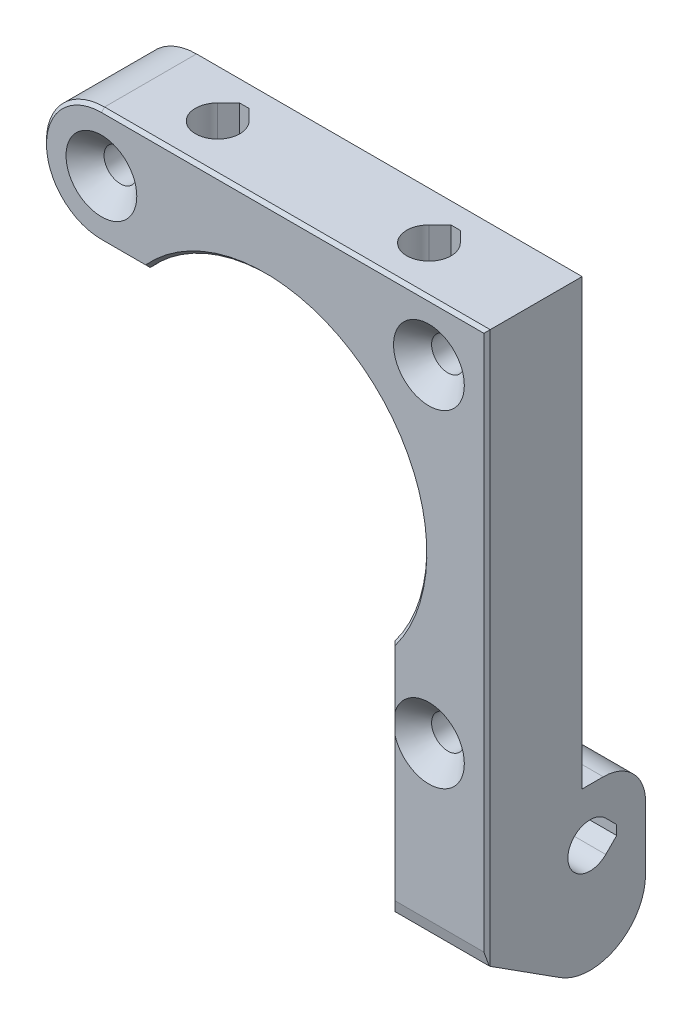
SolidWorks part; units mm, degrees
material "Custom Plastic"
ref_plane "Front Plane" through (0, 0, 0) normal (0, 0, 1) x (1, 0, 0)
ref_plane "Top Plane" through (0, 0, 0) normal (0, 1, 0) x (1, 0, 0)
ref_plane "Right Plane" through (0, 0, 0) normal (1, 0, 0) x (0, 0, -1)
sketch "Sketch1" plane through (0, 0, 0) normal (0, 0, 1) x (1, 0, 0)
  line L0 (-21, 21) -> (21, 21) construction
  line L1 (-21, 21) -> (-21, -21) construction
  line L2 (21, 21) -> (21, -21) construction
  line L3 (-21, -21) -> (21, -21) construction
  line L4 (-21, 21) -> (21, -21) construction
  line L5 (21, 21) -> (-21, -21) construction
  line L7 (-15.5, 10) -> (-11.1803, 10)
  line L8 (-15.5, 21) -> (21, 21)
  line L9 (21, 21) -> (21, -31)
  line L10 (21, -31) -> (12, -31)
  line L11 (12, -31) -> (12, -9)
  line L12 (15.5, 15.5) -> (15.5, -15.5) construction
  line L13 (15.5, 15.5) -> (-22.9774, 15.5) construction
  circle A0 centre (0, 0) radius 11 construction
  arc A1 (12, -9) -> (-11.1803, 10) centre (0, 0) ccw
  circle A2 centre (15.5, 15.5) radius 1.55
  circle A3 centre (15.5, -15.5) radius 1.55
  circle A4 centre (-15.5, 15.5) radius 1.55
  arc A6 (-15.5, 21) -> (-15.5, 10) centre (-15.5, 15.5) ccw
  point P1 (0, 0)
  dimension "D2" = 22
  dimension "D3" = 3.1
  dimension "D5" = 10
  dimension "D7" = 15
  dimension "D1" = 42
  dimension "D4" = 31
  dimension "D6" = 9
extrude "Boss-Extrude1" add sketch "Sketch1" along normal blind 9
sketch "Sketch2" plane through (0, 21, 0) normal (0, 1, 0) x (1, 0, 0)
  line L0 (21, -4.5) -> (-9, -4.5) construction
  line L1 (21, -9) -> (21, 0) construction
  circle A0 centre (-9, -4.5) radius 2.1
  circle A1 centre (11, -4.5) radius 2.1
  dimension "D1" = 4.2
  dimension "D3" = 10
  dimension "D2" = 20
extrude "Cut-Extrude1" cut sketch "Sketch2" against normal blind 14
sketch "Sketch3" plane through (0, 0, 0) normal (0, 0, -1) x (-1, 0, 0)
  line L0 (-12, -9) -> (-12, -31) construction
  line L1 (-21, -31) -> (-12, -31)
  line L2 (-21, -31) -> (-21, -21)
  line L3 (-21, -21) -> (-12, -21)
  line L4 (-12, -31) -> (-12, -21)
  line L5 (-21, 21) -> (15.5, 21) construction
  dimension "D1" = 42
extrude "Boss-Extrude2" add sketch "Sketch3" along normal blind 6
sketch "Sketch4" plane through (21, 0, 0) normal (1, 0, 0) x (0, 0, -1)
  line L0 (6, -26) -> (0.75, -26) construction
  line L1 (6, -21) -> (6, -31) construction
  circle A0 centre (0.75, -26) radius 2.1
  dimension "D1" = 4.2
  dimension "D2" = 0.75
extrude "Cut-Extrude2" cut sketch "Sketch4" against normal through all
sketch "Sketch9" plane through (21, 0, 0) normal (1, 0, 0) x (0, 0, -1)
  line L1 (-9, -31) -> (-2.0769, -35.4239)
  line L2 (-9, -31) -> (6, -31)
  line L3 (0.75, -31) -> (0.75, -26) construction
  arc A0 (-2.0769, -35.4239) -> (6, -31) centre (0.75, -31) ccw
extrude "Boss-Extrude3" add sketch "Sketch9" against normal up to surface (9 mm away) up to face at (12, -26, -2.85)
fillet "Fillet1" radius 4 1 edges at (16.5, -21, -6)
sketch "Sketch5" plane through (0, 21, 0) normal (0, 1, 0) x (1, 0, 0)
  line L0 (-13.1, -4.5) -> (-13.1, 2.1732)
  line L1 (-13.1, 2.1732) -> (-4.9, 2.1732)
  line L2 (-4.9, 2.1732) -> (-4.9, -4.5)
  line L3 (6.9, -4.5) -> (6.9, 2.1892)
  line L4 (6.9, 2.1892) -> (15.1, 2.1892)
  line L5 (15.1, 2.1892) -> (15.1, -4.5)
  arc A0 (6.9, -4.5) -> (15.1, -4.5) centre (11, -4.5) ccw
  arc A1 (-13.1, -4.5) -> (-4.9, -4.5) centre (-9, -4.5) ccw
  circle A2 centre (-9, -4.5) radius 2.1 construction
  circle A3 centre (11, -4.5) radius 2.1 construction
  arc A4 (-4.9, -4.5) -> (-13.1, -4.5) centre (-9, -4.5) ccw construction
  arc A5 (15.1, -4.5) -> (6.9, -4.5) centre (11, -4.5) ccw construction
  dimension "D1" = 8.2
extrude "Cut-Extrude3" cut sketch "Sketch5" against normal blind 13.5 from offset 7.5 offset against normal yes
chamfer "Chamfer1" distance 1.8 angle 45 3 edges at (17.05, -15.5, 9) (-13.95, 15.5, 9) (17.05, 15.5, 9)
chamfer "Chamfer2" distance 2 angle 45 2 edges at (8.9, 13.5, 4.5) (-11.1, 13.5, 4.5)
sketch "Sketch6" plane through (12, 0, 0) normal (-1, 0, 0) x (0, 0, 1)
  line L0 (-0.75, -21.9) -> (-0.75, -21)
  line L1 (-2, -21) -> (0, -21) construction
  line L2 (-0.75, -30.1) -> (-0.75, -37.4727)
  line L4 (-0.75, -21) -> (-10.3659, -21)
  line L5 (-10.3659, -21) -> (-10.3659, -37.4727)
  line L6 (-10.3659, -37.4727) -> (-0.75, -37.4727)
  arc A0 (-0.75, -30.1) -> (-0.75, -21.9) centre (-0.75, -26) ccw
  circle A1 centre (-0.75, -26) radius 2.1 construction
  dimension "D1" = 8.2
extrude "Cut-Extrude4" cut sketch "Sketch6" against normal offset from surface (1.5 mm away) 7.5 up to face at (21, -23.9, -0.75)
chamfer "Chamfer3" distance 2 angle 45 1 edges at (13.5, -28.1, -0.75)
chamfer "Chamfer4" distance 3 distance2 2 2 edges at (12, -33.175, -0.75) (12, -21.45, -0.75) first distance on face at (12, -23.2085, 2.3179)
sketch "Sketch7" plane through (0, 21, 0) normal (0, 1, 0) x (1, 0, 0)
  line L0 (-9, -4.5) -> (-10.4849, -3.0151)
  line L1 (-10.4849, -3.0151) -> (-9.4498, -1.98)
  line L2 (-9.4498, -1.98) -> (-8.5502, -1.98)
  line L3 (-8.5502, -1.98) -> (-7.5151, -3.0151)
  line L4 (-7.5151, -3.0151) -> (-9, -4.5)
  line L5 (-9, -4.5) -> (-9, -1.98) construction
  line L6 (10.5502, -1.98) -> (11.4498, -1.98)
  line L7 (9.5151, -3.0151) -> (10.5502, -1.98)
  line L8 (11.4498, -1.98) -> (12.4849, -3.0151)
  line L9 (11, -4.5) -> (11, -1.98) construction
  line L10 (11, -4.5) -> (9.5151, -3.0151)
  line L11 (12.4849, -3.0151) -> (11, -4.5)
  circle A0 centre (-9, -4.5) radius 2.1 construction
  circle A1 centre (11, -4.5) radius 2.1 construction
  point P5 (-9, -2.4)
  point P12 (11, -2.4)
  dimension "D1" = 0.42
  dimension "D2" = 0.42
extrude "Cut-Extrude5" cut sketch "Sketch7" against normal up to surface (7.5 mm away) up to face at (11, 13.5, 1.225)
sketch "Sketch8" plane through (21, 0, 0) normal (1, 0, 0) x (0, 0, -1)
  line L0 (0.75, -26) -> (2.2349, -24.5151)
  line L1 (2.2349, -24.5151) -> (3.27, -25.5502)
  line L2 (3.27, -25.5502) -> (3.27, -26.4498)
  line L3 (3.27, -26.4498) -> (2.2349, -27.4849)
  line L4 (2.2349, -27.4849) -> (0.75, -26)
  line L5 (0.75, -26) -> (3.27, -26) construction
  circle A0 centre (0.75, -26) radius 2.1 construction
  point P5 (2.85, -26)
  dimension "D1" = 0.42
extrude "Cut-Extrude6" cut sketch "Sketch8" against normal through all
chamfer "Chamfer5" distance 0.3 angle 45 7 edges at (16.5, -31, 9) (21, -5, 9) (12, -20, 9) (9.5088, 11.6009, 9) (-13.3402, 10, 9) (-21, 15.5, 9) (2.75, 21, 9) first distance on face at (15.6231, -33.6322, 4.8808) first distance on face at (21, -26, -1.8562) first distance on face at (12, -22.7189, 4.6833) first distance on face at (3.936, 6.7169, 4.2356) first distance on face at (-13.3348, 10, 5.12) first distance on face at (-18.25, 15.5, 4.5) first distance on face at (11, 21, 3.3938)
